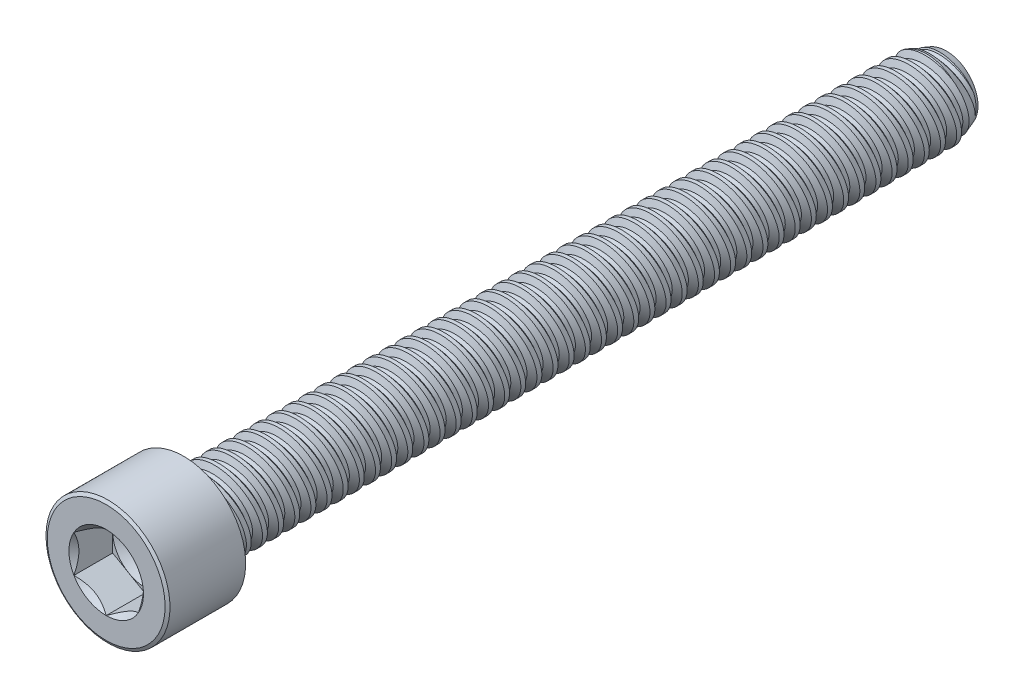
SolidWorks part; units mm, degrees
ref_plane "Front" through (0, 0, 0) normal (0, 0, 1) x (1, 0, 0)
ref_plane "Top" through (0, 0, 0) normal (0, 1, 0) x (1, 0, 0)
ref_plane "Right" through (0, 0, 0) normal (1, 0, 0) x (0, 0, -1)
sketch "Sketch1" plane through (0, 0, 0) normal (1, 0, 0) x (0, 0, -1)
  line L0 (0, 0) -> (-1.5, 0) construction
  line L1 (0, 0) -> (15, 0)
  line L2 (0, 0) -> (0, 0.762)
  line L3 (0, 0.762) -> (15, 0.762)
  line L4 (15, 0) -> (15, 0.762)
  line L5 (0, -0.762) -> (15, -0.762) construction
  dimension "D1" = 1.5
  dimension "Thread Dia" = 1.524
  dimension "Screw Length" = 15
revolve "Revolve1" add sketch "Sketch1" angle 360 about L0
sketch "Sketch2" plane through (0, 0, 0) normal (1, 0, 0) x (0, 0, -1)
  line L0 (0, 0.762) -> (0, -0.762) construction
  line L1 (0, -0.762) -> (0.3175, -0.762) construction
  line L2 (0.3175, -0.762) -> (0, 0.762) construction
  line L3 (0, 0.762) -> (0.0389, 0.7701) construction
  line L4 (0.0389, 0.7701) -> (0.3108, 0.8268)
  line L5 (0.3108, 0.8268) -> (0.2487, 0.6383)
  line L6 (0.2487, 0.6383) -> (0.171, 0.6221)
  line L7 (0.171, 0.6221) -> (0.0389, 0.7701)
  line L8 (0.2099, 0.6302) -> (0.1748, 0.7984) construction
  line L9 (0, -0.762) -> (15, -0.762) construction
  line L10 (0, 0.762) -> (15, 0.762) construction
  line L12 (0.1824, 0.762) -> (0.4999, -0.762) construction
  line L13 (0, -0.0711) -> (0.6824, 0.0711) construction
  line L15 (0, 0) -> (0, 0.762) construction
  point P19 (0.3412, 0)
  dimension "D1" = 60
  dimension "Thread Pitch" = 0.3175
  dimension "D2" = 0.0397
  dimension "D3" = 0.0794
  dimension "D4" = 0.3175
revolve "Cut-Revolve1" cut sketch "Sketch2" angle 360 about L13
sketch "Sketch3" plane through (0, 0, 0) normal (1, 0, 0) x (0, 0, -1)
  line L0 (15, 0.6221) -> (14.6156, 0.762)
  line L1 (14.6156, 0.762) -> (15, 0.762)
  line L2 (15, 0.762) -> (15, 0.6221)
  line L3 (0, 0.762) -> (15, 0.762) construction
  line L4 (15, 0) -> (15, 0.762) construction
  line L5 (14.6156, 0) -> (0, 0) construction
  line L6 (14.6156, 0.762) -> (14.6156, -0.762) construction
  line L7 (0, -0.762) -> (15, -0.762) construction
  dimension "D1" = 20
  dimension "D2" = 1.524
revolve "Cut-Revolve2" cut sketch "Sketch3" angle 360 about L5
pattern_linear "LPattern1" count 47 spacing 0.3175 along (0, 0, -1) of "Cut-Revolve1"
pattern_linear "LPattern2" count 2 spacing 0.3175 along (0, 0, 1) of "Cut-Revolve1"
sketch "Sketch4" plane through (0, 0, 0) normal (0, 0, 1) x (1, 0, 0)
  circle A0 centre (0, 0) radius 1.2192
  dimension "Head Dia" = 2.4384
extrude "Extrude1" add sketch "Sketch4" along normal blind 1.524
chamfer "Chamfer1" distance 0.061 angle 30 1 edges at (1.2192, 0, 1.524) first distance on face at (1.2192, 0, 1.524)
sketch "Sketch6" plane through (0, 0, 1.524) normal (0, 0, 1) x (1, 0, 0)
  line L1 (0, -0.7332) -> (0.635, -0.3666)
  line L2 (0.635, -0.3666) -> (0.635, 0.3666)
  line L3 (0.635, 0.3666) -> (0, 0.7332)
  line L4 (0, 0.7332) -> (-0.635, 0.3666)
  line L5 (-0.635, 0.3666) -> (-0.635, -0.3666)
  line L6 (-0.635, -0.3666) -> (0, -0.7332)
  circle A0 centre (0, 0) radius 0.635 construction
  dimension "Hex" = 1.27
extrude "Cut-Extrude1" cut sketch "Sketch6" against normal blind 0.762
sketch "Sketch7" plane through (0, 0, 1.524) normal (0, 0, 1) x (1, 0, 0)
  circle A0 centre (0, 0) radius 0.7332
extrude "Cut-Extrude4" cut sketch "Sketch7" against normal blind 0.762 draft 45
sketch "Sketch8" plane through (0, 0, 0.762) normal (0, 0, 1) x (1, 0, 0)
  circle A0 centre (0, 0) radius 0.635 construction
  circle A1 centre (0, 0) radius 0.635
extrude "Cut-Extrude5" cut sketch "Sketch8" against normal blind 0.254 draft 60
equation "\"D1@Sketch1\"=\"Screw Length@Sketch1\"/10"
equation "\"D2@Sketch2\"=\"Thread Pitch@Sketch2\"/8"
equation "\"D3@Sketch2\"=\"Thread Pitch@Sketch2\"/4"
equation "\"D4@Sketch2\"=\"Thread Pitch@Sketch2\""
equation "\"D3@LPattern1\"=\"Thread Pitch@Sketch2\""
equation "\"D1@Chamfer1\"=\"Thread Dia@Sketch1\"/25"
equation "\"D1@Cut-Extrude1\"=\"Head Height@Extrude1\"/2"
equation "\"D1@Cut-Extrude4\"=\"D1@Cut-Extrude1\""
equation "\"D1@Cut-Extrude5\"=\"D1@Cut-Extrude1\"/3"
equation "\"D1@LPattern1\"=\"Screw Length@Sketch1\"/\"Thread Pitch@Sketch2\""
equation "\"D3@LPattern2\"=\"Thread Pitch@Sketch2\""
